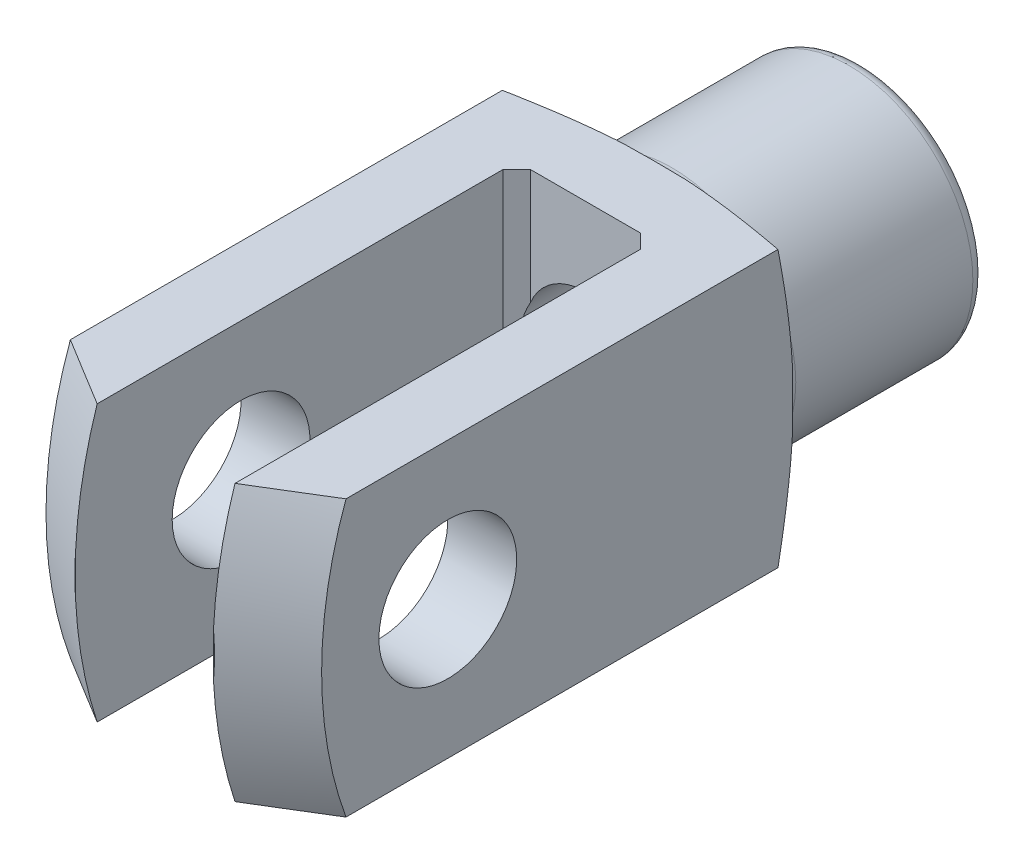
SolidWorks part; units mm, degrees
ref_plane "Front Plane" through (0, 0, 0) normal (0, 0, 1) x (1, 0, 0)
ref_plane "Top Plane" through (0, 0, 0) normal (0, 1, 0) x (1, 0, 0)
ref_plane "Right Plane" through (0, 0, 0) normal (1, 0, 0) x (0, 0, -1)
ref_plane "Plane1" through (0, 0, 0) normal (1, 0, 0) x (0, 0, -1)
sketch "Sketch1" plane through (0, 0, 0) normal (1, 0, 0) x (0, 0, -1)
  line L0 (-12, 0) -> (-12, 20)
  line L1 (-12, 20) -> (22.3875, 20)
  line L2 (22.3875, 20) -> (25, 10.25)
  line L3 (26.25, 9) -> (39.1, 9)
  line L4 (40, 8.1) -> (40, 0)
  line L5 (40, 0) -> (-12, 0)
  line L6 (40, 0) -> (-12, 0) construction
  arc A0 (25, 10.25) -> (26.25, 9) centre (26.25, 10.25) ccw
  arc A1 (39.1, 9) -> (40, 8.1) centre (39.1, 8.1) cw
revolve "Revolve1" add sketch "Sketch1" angle 360 about L6 reverse direction yes
ref_plane "Plane2" through (0, 0, 0) normal (0, 1, 0) x (1, 0, 0)
sketch "Sketch2" plane through (0, 0, 0) normal (0, 1, 0) x (1, 0, 0)
  line L0 (-5, 19) -> (-5, -13)
  line L1 (-5, -13) -> (5, -13)
  line L2 (5, -13) -> (5, 19)
  line L3 (5, 19) -> (4, 20)
  line L4 (4, 20) -> (-4, 20)
  line L5 (-4, 20) -> (-5, 19)
extrude "Cut-Extrude1" cut sketch "Sketch2" against normal blind 21 and the other way blind 21
ref_plane "Plane3" through (0, 0, 0) normal (1, 0, 0) x (0, 0, -1)
sketch "Sketch3" plane through (0, 0, 0) normal (1, 0, 0) x (0, 0, -1)
  line L0 (-33, -30) -> (40, -30)
  line L1 (40, -30) -> (40, -10)
  line L2 (40, -10) -> (-13, -10)
  line L3 (-13, -10) -> (-13, 10)
  line L4 (-13, 10) -> (40, 10)
  line L5 (40, 10) -> (40, 30)
  line L6 (40, 30) -> (-33, 30)
  line L7 (-33, 30) -> (-33, -30)
extrude "Cut-Extrude2" cut sketch "Sketch3" against normal blind 21 and the other way blind 21
ref_plane "Plane4" through (0, 0, 0) normal (0, 1, 0) x (1, 0, 0)
sketch "Sketch4" plane through (0, 0, 0) normal (0, 1, 0) x (1, 0, 0)
  line L0 (-30, -33) -> (30, -33)
  line L1 (30, -33) -> (30, 40)
  line L2 (30, 40) -> (10, 40)
  line L3 (10, 40) -> (10, -13)
  line L4 (10, -13) -> (-10, -13)
  line L5 (-10, -13) -> (-10, 40)
  line L6 (-10, 40) -> (-30, 40)
  line L7 (-30, 40) -> (-30, -33)
extrude "Cut-Extrude3" cut sketch "Sketch4" against normal blind 21 and the other way blind 21
ref_plane "Plane5" through (0, 0, 0) normal (0, 0, 1) x (1, 0, 0)
sketch "Sketch5" plane through (0, 0, 0) normal (0, 0, 1) x (1, 0, 0)
  line L0 (-13, 0) -> (-13, 5)
  line L1 (-13, 5) -> (13, 5)
  line L2 (13, 5) -> (13, 0)
  line L3 (13, 0) -> (-13, 0)
  line L4 (13, 0) -> (-13, 0) construction
revolve "Cut-Revolve1" cut sketch "Sketch5" angle 360 about L4 reverse direction yes
ref_plane "Plane6" through (0, 0, 0) normal (1, 0, 0) x (0, 0, -1)
sketch "Sketch6" plane through (0, 0, 0) normal (1, 0, 0) x (0, 0, -1)
  line L0 (18.9, 0) -> (18.9, 4.3235)
  line L1 (18.9, 4.3235) -> (39.4235, 4.3235)
  line L2 (39.4235, 4.3235) -> (40.1, 5)
  line L3 (40.1, 5) -> (40.1, 0)
  line L4 (40.1, 0) -> (18.9, 0)
  line L5 (40.1, 0) -> (18.9, 0) construction
revolve "Cut-Revolve2" cut sketch "Sketch6" angle 360 about L5 reverse direction yes
cosmetic thread "Cosmetic Thread1" parameters "D1"=17.7, "D2"=10
ref_plane "Plane7" through (0, 0, 0) normal (0, 1, 0) x (1, 0, 0)
sketch "Sketch7" plane through (0, 0, 0) normal (0, 1, 0) x (1, 0, 0)
  line L0 (-12, -8.0008) -> (-12, -31.0948)
  line L1 (-12, -31.0948) -> (0, -38.023)
  line L2 (0, -38.023) -> (12, -31.0948)
  line L3 (12, -31.0948) -> (12, -8.0008)
  line L4 (12, -8.0008) -> (0, -14.929)
  line L5 (0, -14.929) -> (-12, -8.0008)
  line L6 (-12, 20) -> (12, 20) construction
revolve "Cut-Revolve3" cut sketch "Sketch7" angle 90 about L6 other way angle 90 reverse direction yes
